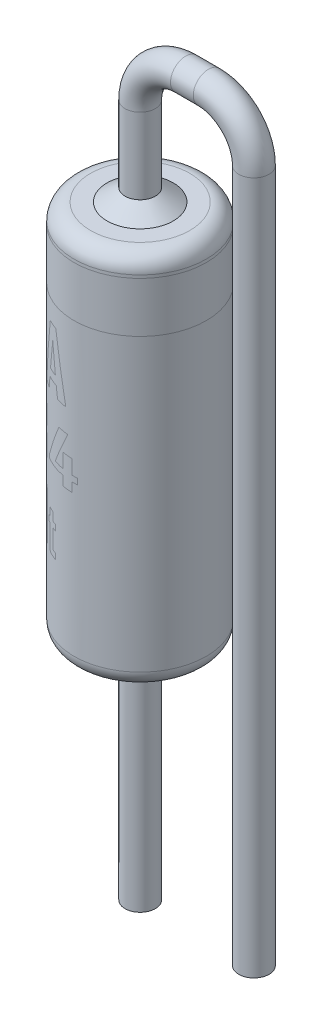
SolidWorks part; units mm, degrees
ref_plane "Front Plane" through (0, 0, 0) normal (0, 0, 1) x (1, 0, 0)
ref_plane "Top Plane" through (0, 0, 0) normal (0, 1, 0) x (1, 0, 0)
ref_plane "Right Plane" through (0, 0, 0) normal (1, 0, 0) x (0, 0, -1)
ref_plane "BODY_RPlane" through (0, 0, 0) normal (1, 0, 0) x (0, 0, -1)
sketch "Sketch10" plane through (0, 0, 0) normal (0, 0, 1) x (1, 0, 0)
  line L1 (-0.8306, 7.525) -> (-0.5538, 7.525)
  line L3 (0, 4.3675) -> (-1.1075, 4.3675) construction
  line L12 (-1.1075, 1.4869) -> (-1.1075, 7.2481)
  line L14 (-0.7076, 1.21) -> (-0.1163, 1.21) construction
  line L15 (-0.5537, 1.21) -> (-0.5537, 4.3675) construction
  line L16 (-0.8306, 1.21) -> (-0.5537, 1.21)
  line L17 (-0.5537, 1.21) -> (-0.5538, 7.525)
  line L18 (0, 1) -> (0, 7.735) construction
  arc A6 (-1.1075, 1.4869) -> (-0.8306, 1.21) centre (-0.8306, 1.4869) ccw
  arc A8 (-1.1075, 7.2481) -> (-0.8306, 7.525) centre (-0.8306, 7.2481) cw
  point P22 (0, 4.3675)
  point P30 (-1.1075, 4.3675)
  point P31 (-0.5537, 4.3675)
  point P34 (-1.1075, 4.3675)
  dimension "D8" = 0.2769
  dimension "D1" = 6.735
  dimension "D7" = 1.1075
  dimension "D9" = 0.21
  dimension "D10" = 0.5537
  dimension "D2" = 4.3675
revolve "BODY_main" add sketch "Sketch10" angle 360 about L18
sketch "Sketch11" plane through (0, 0, 0) normal (0, 0, 1) x (1, 0, 0)
  line L4 (0, 1.21) -> (0, 1)
  line L17 (-200000.7076, 1.21) -> (199999.8837, 1.21) construction
  line L18 (0, 1) -> (0, 7.735) construction
  line L19 (0, 1) -> (-0.254, 1)
  line L20 (-0.254, 1) -> (-0.5537, 1.21)
  line L21 (-0.5537, 1.21) -> (0, 1.21)
  line L22 (-1.1075, 4.3675) -> (0, 4.3675) construction
  line L23 (-0.5537, 7.525) -> (0, 7.525)
  line L24 (-0.254, 7.735) -> (-0.5537, 7.525)
  line L25 (0, 7.735) -> (-0.254, 7.735)
  line L26 (0, 7.525) -> (0, 7.735)
  dimension "D3" = 0.254
revolve "BODY_to_PIN" add sketch "Sketch11" angle 360 about L18
ref_plane "TEXT_plane" through (-1.2075, 0, 0) normal (1, 0, 0) x (0, 0, -1)
sketch "Sketch4"
  dimension "D1" = 6.9586
  dimension "D3" = 0.8419
  dimension "D5" = 0.05
  dimension "D6" = 0.15
  dimension "D2" = 5
wrap "TEXT_Wrap" sketch "Sketch4" wrap type scribe source sketch "Sketch4" face at (1.1075, 1.4869, 0)
sketch "Sketch6" plane through (1, 1, 0) normal (0, 1, 0) x (0, 0, -1)
  circle A0 centre (0, 1) radius 0.254
  dimension "D1" = 0.508
sketch "Sketch7" plane through (0, 0, 0) normal (0, 0, 1) x (1, 0, 0)
  line L0 (1.143, 9.767) -> (0.762, 9.767)
  line L1 (0, 9.005) -> (0, -2.6)
  line L2 (0.9525, 9.767) -> (0.9525, -2.6) construction
  line L3 (0, -2.6) -> (0.9525, -2.6) construction
  line L6 (1.905, 9.005) -> (1.905, -2.6)
  line L7 (0, -4.1102) -> (0, 4.1102) construction
  line L8 (0.254, 7.735) -> (-0.254, 7.735) construction
  arc A0 (0.762, 9.767) -> (0, 9.005) centre (0.762, 9.005) ccw
  arc A1 (1.143, 9.767) -> (1.905, 9.005) centre (1.143, 9.005) cw
  point P11 (0, 7.735)
  dimension "D3" = 0.762
  dimension "D1" = 2.6
  dimension "D2" = 2.032
sweep "PINS" add profiles "Sketch6" path "Sketch7"
equation "\"D4@Sketch7\"=\"PIN_PITCH\""
equation "\"pin_config-----------------\"= 0x000000000000000000000000000000000"
equation "\"PIN_PITCH\"= 75mil"
equation "\"PCB_standoff\"= 1mm"
equation "\"PCB_thickness\"= 1.6mm"
equation "\"PCB_bottom_lead\"= 1.0mm"
equation "\"PIN_C_max\"= 0.558mm"
equation "\"PIN_C_min\"= 0.458mm"
equation "\"body_config----------------\"= 0x000000000000000000000000000000000"
equation "\"BODY_B_max\"= 7.62mm"
equation "\"BODY_B_min\"= 5.85mm"
equation "\"BODY_D_max\"= 2.27mm"
equation "\"BODY_D_min\"= 2.16mm"
equation "\"part_config----------------\"= 0x000000000000000000000000000000000"
equation "\"Component_Size\"= 1"
equation "\"Component_Type\"= 0'variable is not used"
equation "\"auto_calc-------------------\"= 0x000000000000000000000000000000000"
equation "\"BODY_B\"= IIF ( \"Component_Size\" > 0 , IIF ( \"Component_Size\" = 1 , ( ( \"BODY_B_max\" + \"BODY_B_min\" ) / 2 ) , \"BODY_B_max\" ) , \"BODY_B_min\" )'NOT_FOR_USER , AUTOMATIC CALCULATION"
equation "\"BODY_D\"= IIF ( \"Component_Size\" > 0 , IIF ( \"Component_Size\" = 1 , ( ( \"BODY_D_max\" + \"BODY_D_min\" ) / 2 ) , \"BODY_D_max\" ) , \"BODY_D_min\" )'NOT_FOR_USER , AUTOMATIC CALCULATION"
equation "\"PIN_C\"= IIF ( \"Component_Size\" > 0 , IIF ( \"Component_Size\" = 1 , ( ( \"PIN_C_max\" + \"PIN_C_min\" ) / 2 ) , \"PIN_C_max\" ) , \"PIN_C_min\" )'NOT_FOR_USER , AUTOMATIC CALCULATION"
equation "\"PIN_L\"= \"PCB_thickness\" + \"PCB_bottom_lead\"'NOT_FOR_USER , AUTOMATIC CALCULATION"
equation "\"PIN_R\"= \"PIN_C\" * 1.5'NOT_FOR_USER , AUTOMATIC CALCULATION"
equation "\"D1@TEXT_plane\"=\"BODY_D\"/2 + 0.1"
equation "\"D1@Sketch4\"=\"BODY_D\" * pi"
equation "\"BODY_CATM_H1\"= \"BODY_B\" / 8'NOT_FOR_USER , AUTOMATIC CALCULATION"
equation "\"D1@Sketch6\"=\"PIN_C\""
equation "\"D3@Sketch7\"=\"PIN_R\""
equation "\"D1@Sketch7\"=\"PIN_L\""
equation "\"D3@Sketch4\"=\"BODY_CATM_H1\""
equation "\"D1@Sketch10\"=\"BODY_B\""
equation "\"D7@Sketch10\"=\"BODY_D\"/2"
equation "\"D8@Sketch10\"=\"BODY_D\"/8"
equation "\"D10@Sketch10\"=\"BODY_D\"/4"
equation "\"D2@Sketch10\"=\"BODY_B\"/2 + \"PCB_standoff\""
equation "\"D3@Sketch11\"=\"PIN_C\"/2"
equation "\"D2@Sketch7\"= \"PIN_C\" * 4"
